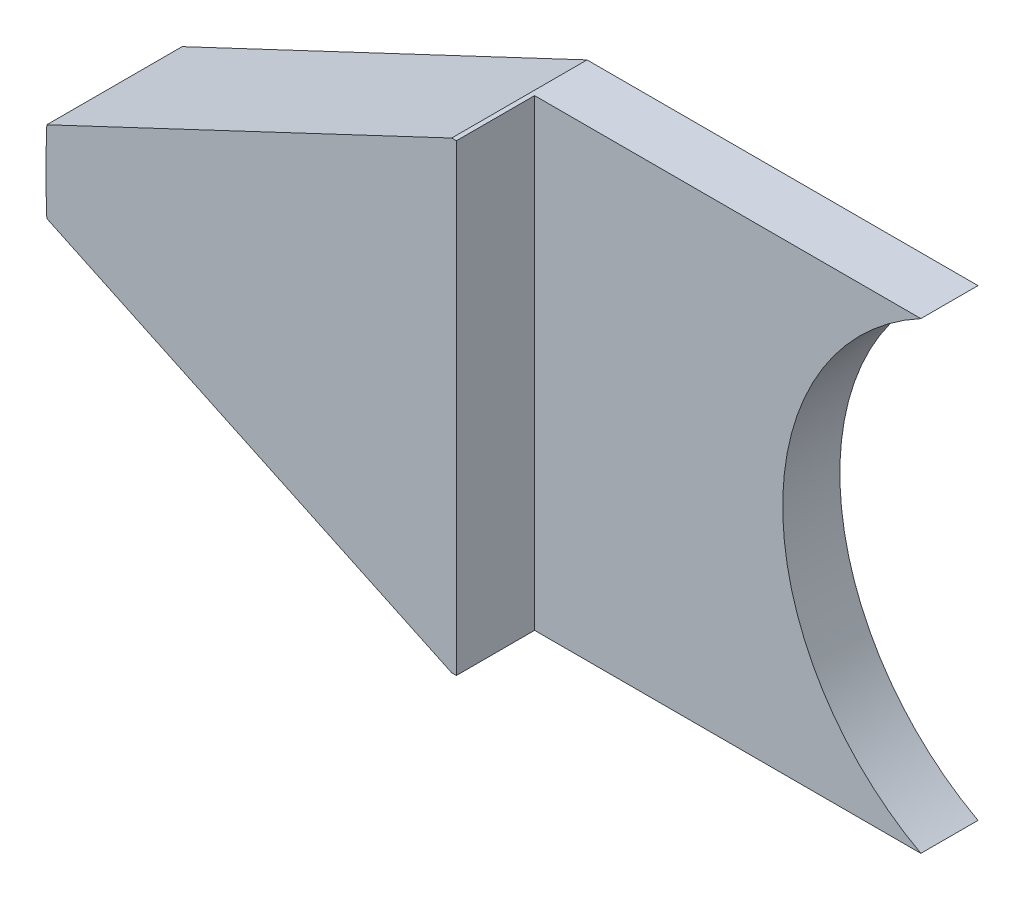
SolidWorks part; units mm, degrees
note: The reader was unsure of these and kept them because the rebuilt part matched: shared geometry of "Эскиз2<5>".
ref_plane "Спереди" through (0, 0, 0) normal (0, 0, 1) x (1, 0, 0)
ref_plane "Сверху" through (0, 0, 0) normal (0, 1, 0) x (1, 0, 0)
ref_plane "Справа" through (0, 0, 0) normal (1, 0, 0) x (0, 0, -1)
sketch "Эскиз1" plane through (0, 0, 0) normal (0, 0, 1) x (1, 0, 0)
  line L0 (-8.75, 0) -> (-30.65, 0) construction
  line L1 (-17.156, -7.7) -> (-30.6203, -1.35)
  line L2 (-17.156, 7.7) -> (-30.6203, 1.35)
  line L3 (-17.156, 7.7) -> (-4.156, 7.7)
  line L7 (-17.156, -7.7) -> (-4.156, -7.7)
  arc A3 (-4.156, 7.7) -> (-4.156, -7.7) centre (0, 0) ccw
  arc A4 (-30.6203, -1.35) -> (-30.6203, 1.35) centre (0, 0) cw
  point P9 (-30.65, 0)
  dimension "D2" = 8.75
  dimension "D4" = 30.65
  dimension "D1" = 2.7
  dimension "D3" = 13
  dimension "D5" = 15.4
extrude "Бобышка-Вытянуть1" add sketch "Эскиз1" along normal blind 7
sketch "Эскиз2" plane through (0, 0, 7) normal (0, 0, 1) x (1, 0, 0)
  line L1 (-17.156, -7.7) -> (-4.156, -7.7) construction
  line L4 (-17, 7.7) -> (-17, -7.7)
  line L31 (-4.156, 7.7) -> (-17.156, 7.7) construction
  arc A0 (-30.6203, -1.35) -> (-30.6203, 1.35) centre (0, 0) cw
  point P32 (-8.6542, 5.1259)
  point P33 (-6.8191, 0)
  point P40 (-6.8191, -5.125)
  dimension "D1" = 17
extrude "Вырез-Вытянуть1" cut sketch "Эскиз2" against normal blind 5.1
extrude "Вырез-Вытянуть2" cut sketch "Эскиз2<5>" against normal blind 2.5
sketch "Эскиз2<5>" plane through (0, 0, 7) normal (0, 0, 1) x (1, 0, 0) same geometry as "Эскиз2"
